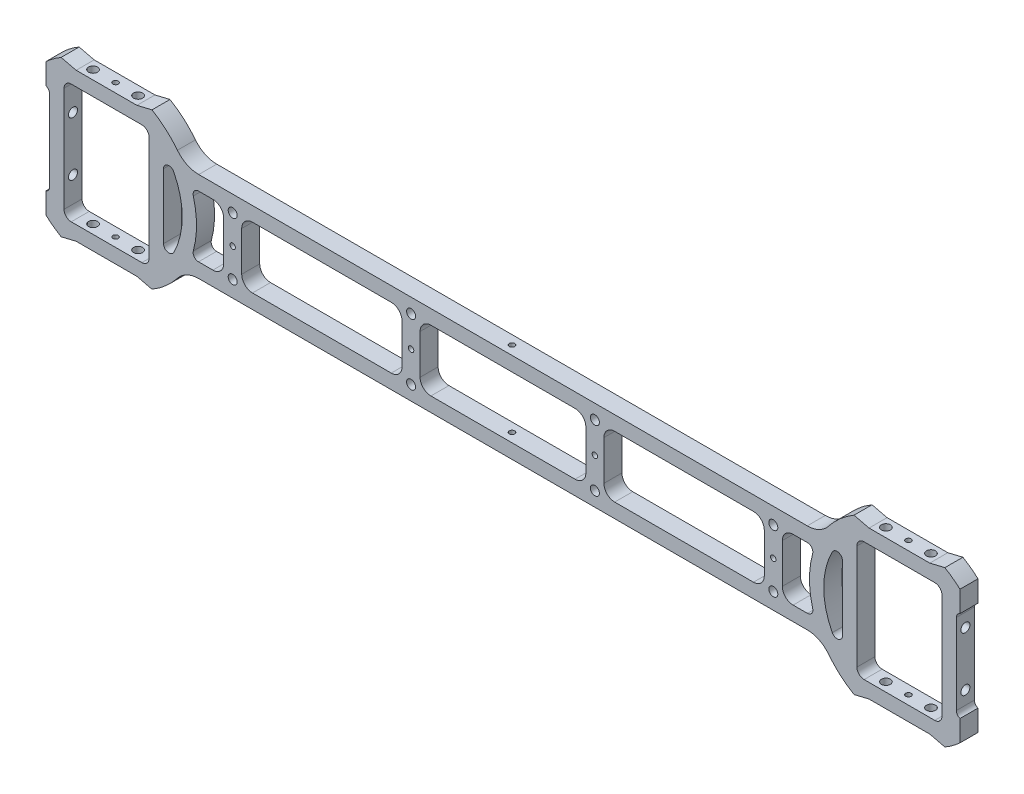
SolidWorks part; units mm, degrees
ref_plane "前视基准面" through (0, 0, 0) normal (0, 0, 1) x (1, 0, 0)
ref_plane "上视基准面" through (0, 0, 0) normal (0, 1, 0) x (1, 0, 0)
ref_plane "右视基准面" through (0, 0, 0) normal (1, 0, 0) x (0, 0, -1)
sketch "草图1" plane through (0, 0, 0) normal (0, 0, 1) x (1, 0, 0)
  line L0 (0, -114.9603) -> (0, 164.1005) construction
  line L1 (-220, -25) -> (0, -25)
  line L2 (-220, 25) -> (0, 25)
  line L3 (-220, 0) -> (-220, 65.4164) construction
  line L4 (-210, 0) -> (-106.141, 0) construction
  line L5 (-243.6, -33.1) -> (-243.6, 33.1)
  line L6 (-243.6, 33.1) -> (-196.4, 33.1)
  line L7 (-196.4, -33.1) -> (-196.4, 33.1)
  line L8 (-243.6, -33.1) -> (-196.4, -33.1)
  line L9 (-251.6, 0) -> (-251.6, 50.4262) construction
  line L10 (-251.6, 27.6666) -> (-251.6, -27.6666)
  line L11 (-188.4, 27.6666) -> (-188.4, -27.6666)
  line L12 (-210, 41.1) -> (-130.0604, 41.1) construction
  line L13 (-236.8462, 41.1) -> (-203.1538, 41.1)
  line L14 (-236.8462, -41.1) -> (-203.1538, -41.1)
  line L15 (0, 25) -> (0, -25)
  line L16 (-173.0503, 17) -> (0, 17)
  line L17 (-173.0503, -17) -> (0, -17)
  line L18 (-51, 65.5435) -> (-51, -65.4943) construction
  line L19 (-150, -63.787) -> (-150, 61.0618) construction
  line L20 (-56, 25) -> (-56, -25)
  line L21 (-46, 25) -> (-46, -25)
  line L22 (-155, 25) -> (-155, -25)
  line L23 (-145, 25) -> (-145, -25)
  line L24 (-183.4, 5.4259) -> (-183.4, -5.4259)
  line L25 (-245.2123, 43.1) -> (-230.7422, 43.1)
  line L26 (-245.2123, -43.1) -> (-230.7422, -43.1)
  line L27 (-51, 43.1) -> (907.4, 43.1)
  line L28 (-253.6, -36.9366) -> (-253.6, -25.2)
  line L29 (-253.6, 25.2) -> (-253.6, 36.9366)
  line L30 (-209.2578, -43.1) -> (-194.7877, -43.1)
  line L31 (-209.2578, 43.1) -> (-194.7877, 43.1)
  line L32 (-236.8462, 41.1) -> (-245.2123, 43.1)
  line L33 (-203.1538, 41.1) -> (-194.7877, 43.1)
  line L34 (-203.1538, -41.1) -> (-194.7877, -43.1)
  line L35 (-236.8462, -41.1) -> (-245.2123, -43.1)
  circle A0 centre (-220, 0) radius 25 construction
  arc A1 (-253.6, -36.9366) -> (-245.2123, -43.1) centre (-220, 0) ccw
  arc A2 (-251.6, -27.6666) -> (-253.6, -25.2) centre (-220, 0) cw
  arc A3 (-188.4, -27.6666) -> (-188.4, 27.6666) centre (-220, 0) ccw
  arc A4 (-236.8462, 41.1) -> (-230.7422, 43.1) centre (-220, 0) cw
  arc A5 (-236.8462, -41.1) -> (-230.7422, -43.1) centre (-220, 0) ccw
  circle A6 centre (-150, 19) radius 2.5
  circle A7 centre (-51, 17) radius 2.5
  circle A10 centre (-51, -17) radius 2.5
  circle A11 centre (-150, -19) radius 2.5
  arc A12 (-183.4, -5.4259) -> (-183.4, 5.4259) centre (-220, 0) ccw
  circle A13 centre (-51, 0) radius 1.5
  circle A14 centre (-150, 0) radius 1.5
  arc A15 (-253.6, 25.2) -> (-251.6, 27.6666) centre (-220, 0) cw
  arc A16 (-194.7877, -43.1) -> (-194.7877, 43.1) centre (-220, 0) ccw
  arc A17 (-209.2578, -43.1) -> (-203.1538, -41.1) centre (-220, 0) ccw
  arc A18 (-245.2123, 43.1) -> (-253.6, 36.9366) centre (-220, 0) ccw
  arc A19 (-209.2578, 43.1) -> (-203.1538, 41.1) centre (-220, 0) cw
  point P17 (-220, 33.1)
  point P19 (-196.4, 0)
  point P20 (-243.6, 0)
  dimension "D2" = 50
  dimension "D5" = 8
  dimension "D6" = 8
  dimension "D7" = 8
  dimension "D10" = 5
  dimension "D12" = 6
  dimension "D14" = 5
  dimension "D15" = 10
  dimension "D16" = 10
  dimension "D1" = 220
  dimension "D3" = 33.1
  dimension "D4" = 23.6
  dimension "D8" = 51
  dimension "D9" = 150
  dimension "D11" = 5
  dimension "D13" = 8
extrude "凸台-拉伸1" add sketch "草图1" along normal blind 10 contours A3 L1 A1 L2 | A3 L2 A1 L1 L11 L7 L8 L5 L6 A5 L14 L10 A2 L13 A4 | L11 L2 L7 L1 | A1 L16 L22 L2 | L23 L2 L22 L16 | L2 L23 L16 L20 | L21 L2 L20 L16 | L2 L21 L16 L15 | L17 L21 L1 L15 | L21 L17 L20 L1 | L17 L23 L1 L20 | L23 L17 L22 L1 | A1 L1 L22 L17 | L23 L16 L22 L17 A6 | L21 L16 L20 L17 region at (-150, -21.5698, 0) region at (-164.9141, -21.1254, 0) region at (-100.5, -21, 0) region at (-185.424, -34.4063, 0) region at (-176.5514, 0, 0) region at (-154.6456, 0, 0) region at (-51, -21.4111, 0) region at (-150, 21.5698, 0) region at (-164.9141, 21.1254, 0) region at (-23, -21, 0) region at (-55.6456, 0, 0) region at (-100.5, 21, 0) region at (-192.4, 0, 0) region at (-51, 21.4111, 0) region at (-23, 21, 0)
fillet "圆角1" radius 4 4 edges at (-243.6, -33.1, 5) (-196.4, -33.1, 5) (-196.4, 33.1, 5) (-243.6, 33.1, 5)
fillet "圆角4" radius 6 8 edges at (-46, 17, 5) (-46, -17, 5) (-56, 17, 5) (-56, -17, 5) (-145, 17, 5) (-145, -17, 5) (-155, -17, 5) (-155, 17, 5)
fillet "圆角7" radius 3 2 edges at (-251.6, -27.6666, 5) (-251.6, 27.6666, 5)
fillet "圆角8" radius 3 2 edges at (-188.4, 27.6666, 5) (-188.4, -27.6666, 5)
sketch "草图2" plane through (0, 0, 0) normal (0, 1, 0) x (1, 0, 0)
  line L0 (-220, -10) -> (-220, 0) construction
  line L1 (-239.6, -10) -> (-200.4, -10) construction
  line L2 (-239.6, 0) -> (-200.4, 0) construction
  line L3 (-215.8574, -5) -> (-202.3716, -5) construction
  circle A0 centre (-232.5, -5) radius 2.5
  circle A1 centre (-207.5, -5) radius 2.5
  circle A2 centre (-220, -5) radius 1.5
  dimension "D1" = 12.5
extrude "切除-拉伸1" cut sketch "草图2" against normal through all and the other way through all
sketch "草图3" plane through (-243.6, 0, 0) normal (1, 0, 0) x (0, 0, -1)
  line L0 (0, 0) -> (-10, 0) construction
  line L1 (-10, -29.1) -> (-10, 29.1) construction
  line L2 (-5, -6.432) -> (-5, 14.1737) construction
  circle A0 centre (-5, 15) radius 2.5
  circle A1 centre (-5, -15) radius 2.5
  dimension "D1" = 15
extrude "切除-拉伸2" cut sketch "草图3" against normal blind 30
sketch "草图4" plane through (0, 25, 0) normal (0, 1, 0) x (1, 0, 0)
  line L0 (0, -10) -> (0, 0) construction
  circle A0 centre (0, -5) radius 1.5
extrude "切除-拉伸3" cut sketch "草图4" against normal through all
fillet "圆角10" radius 15 2 edges at (-176.7765, -25, 5) (-176.7765, 25, 5)
fillet "圆角11" radius 3 2 edges at (-173.0503, -17, 5) (-173.0503, 17, 5)
mirror "镜向1" about plane through (0, 0, 10) normal (1, 0, 0) of "切除-拉伸3", "圆角11", "凸台-拉伸1", "圆角4", "圆角8", "圆角1", "圆角7", "切除-拉伸1", "切除-拉伸2", "圆角10"
sketch "草图5" plane through (0, 0, 0) normal (0, 0, -1) x (-1, 0, 0)
  circle A0 centre (150, 19) radius 2.5
  circle A1 centre (150, -19) radius 2.5
  circle A2 centre (-150, -19) radius 2.5
  circle A3 centre (-150, 19) radius 2.5
extrude "凸台-拉伸2" add sketch "草图5" against normal blind 10
sketch "草图6" plane through (0, 0, 0) normal (0, 0, -1) x (-1, 0, 0)
  circle A0 centre (-150, 16) radius 2.5
  circle A1 centre (-150, -16) radius 2.5
  circle A2 centre (48, -16) radius 2.5
  circle A3 centre (48, 16) radius 2.5
extrude "切除-拉伸4" cut sketch "草图6" against normal blind 10
sketch "草图7" plane through (0, 0, 0) normal (0, 0, -1) x (-1, 0, 0)
  arc A0 (48.8876, 18.3371) -> (50.1124, 14.6629) centre (48, 16) ccw
  arc A1 (48.8876, 18.3371) -> (50.1124, 14.6629) centre (51, 17) ccw
  arc A2 (50.1124, -14.6629) -> (48.8876, -18.3371) centre (51, -17) ccw
  arc A3 (50.1124, -14.6629) -> (48.8876, -18.3371) centre (48, -16) ccw
extrude "凸台-拉伸3" add sketch "草图7" against normal blind 10
sketch "草图8" plane through (0, 0, 0) normal (0, 0, -1) x (-1, 0, 0)
  circle A0 centre (-150, 16) radius 2.5
  circle A1 centre (-150, -16) radius 2.5
  circle A2 centre (150, -16) radius 2.5
  circle A3 centre (150, 16) radius 2.5
extrude "切除-拉伸5" cut sketch "草图8" against normal blind 10
